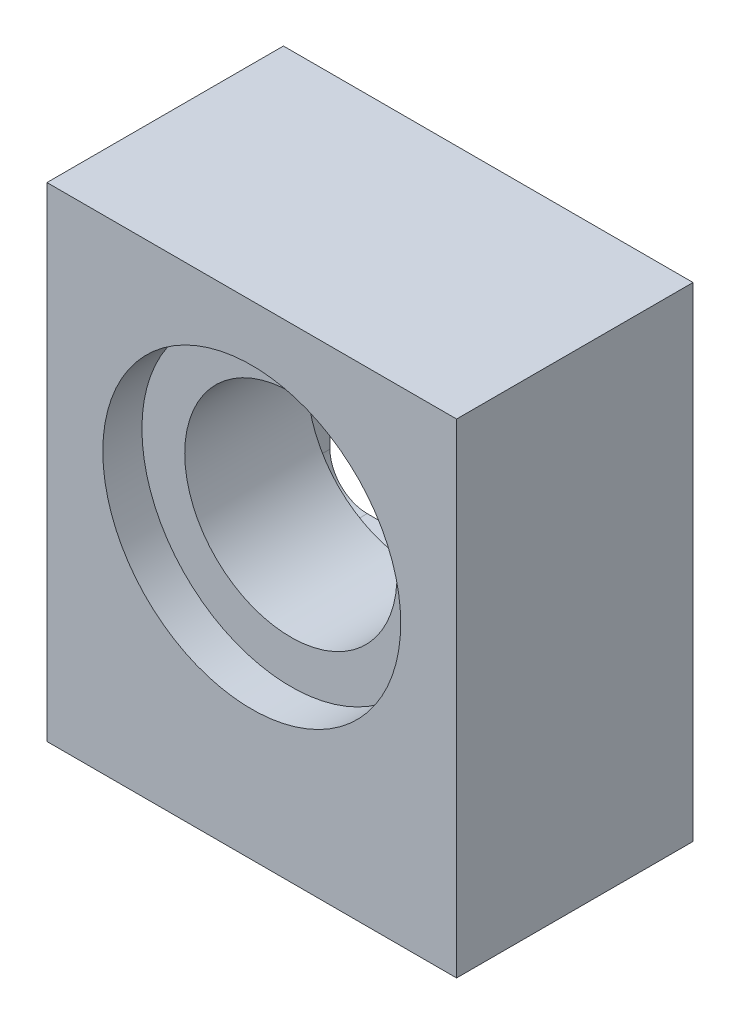
SolidWorks part; units mm, degrees
ref_plane "Front Plane" through (0, 0, 0) normal (0, 0, 1) x (1, 0, 0)
ref_plane "Top Plane" through (0, 0, 0) normal (0, 1, 0) x (1, 0, 0)
ref_plane "Right Plane" through (0, 0, 0) normal (1, 0, 0) x (0, 0, -1)
sketch "Sketch1" plane through (0, 0, 0) normal (0, 0, 1) x (1, 0, 0)
  line L1 (0, 0) -> (22, 0)
  line L2 (0, 0) -> (0, 26)
  line L3 (0, 26) -> (22, 26)
  line L4 (22, 0) -> (22, 26)
  circle A0 centre (11, 15) radius 5.7
  dimension "D5" = 11.4
  dimension "D1" = 22
  dimension "D2" = 26
  dimension "D3" = 11
  dimension "D4" = 15
extrude "Boss-Extrude1" add sketch "Sketch1" along normal blind 12.7
sketch "Sketch2" plane through (0, 0, 0) normal (0, 0, 1) x (1, 0, 0)
  line L1 (4.5, 23.5) -> (17.5, 23.5)
  line L2 (2.5, 21.5) -> (2.5, 8.5)
  line L3 (4.5, 6.5) -> (17.5, 6.5)
  line L4 (19.5, 21.5) -> (19.5, 8.5)
  line L5 (2.5, 23.5) -> (19.5, 6.5) construction
  line L6 (2.5, 6.5) -> (19.5, 23.5) construction
  arc A0 (2.5, 8.5) -> (4.5, 6.5) centre (4.5, 8.5) ccw
  arc A1 (17.5, 6.5) -> (19.5, 8.5) centre (17.5, 8.5) ccw
  arc A2 (17.5, 23.5) -> (19.5, 21.5) centre (17.5, 21.5) cw
  arc A3 (4.5, 23.5) -> (2.5, 21.5) centre (4.5, 21.5) ccw
  point P0 (11, 15)
  dimension "D2" = 2
  dimension "D1" = 17
extrude "Cut-Extrude1" cut sketch "Sketch2" along normal blind 4
sketch "Sketch3" plane through (0, 0, 12.7) normal (0, 0, -1) x (-1, 0, 0)
  circle A0 centre (-11, 15) radius 8
  dimension "D1" = 16
extrude "Cut-Extrude2" cut sketch "Sketch3" along normal blind 2.1
hole_wizard "Tap Drill for M3x0.5 Tap1" positions "Sketch5" profile "Sketch4" hole size "M3x0.5" standard "ANSI Metric"
sketch "Sketch5" plane through (0, 0, 0) normal (0, -1, 0) x (-1, 0, 0)
  line L0 (0, 0) -> (-22, 0) construction
  line L1 (-22, -12.7) -> (-22, 0) construction
  line L3 (-18, -3) -> (-4, -3) construction
  line L4 (-18, -3) -> (-18, -9.7) construction
  line L5 (-18, -9.7) -> (-4, -9.7) construction
  line L6 (-4, -3) -> (-4, -9.7) construction
  line L7 (0, -12.7) -> (-22, -12.7) construction
  line L8 (0, -12.7) -> (0, 0) construction
  point P0 (-18, -3)
  point P2 (-4, -3)
  point P4 (-4, -9.7)
  point P6 (-18, -9.7)
  point P8 (-11, -6.35)
  dimension "D1" = 6.35
  dimension "D2" = 4
  dimension "D3" = 3
  dimension "D4" = 3
  dimension "D5" = 11
  dimension "D6" = 4
sketch "Sketch4" plane through (18, 0, 3) normal (1, 0, 0) x (0, 0, -1)
  line L0 (0, 0) -> (0, 5.7511)
  line L1 (0, 5.7511) -> (1.25, 5)
  line L2 (1.25, 5) -> (1.25, 0)
  line L5 (1.25, 0) -> (0, 0)
  line L10 (0, 5.7511) -> (-1.25, 5) construction
  line L11 (0, -6.35) -> (0, 107.95) construction
  dimension "Hole Dia." = 2.5
  dimension "Hole Depth" = 5
  dimension "Drill Angle" = 118
